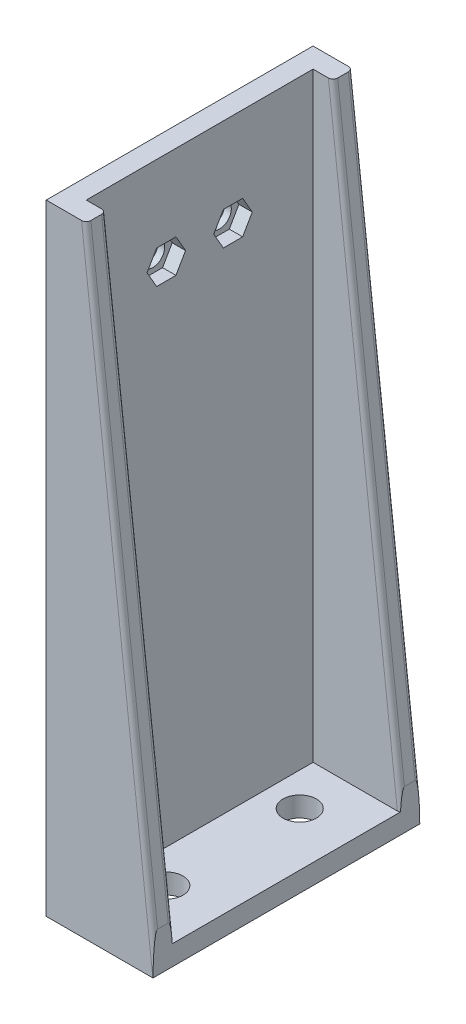
SolidWorks part; units mm, degrees
ref_plane "Front Plane" through (0, 0, 0) normal (0, 0, 1) x (1, 0, 0)
ref_plane "Top Plane" through (0, 0, 0) normal (0, 1, 0) x (1, 0, 0)
ref_plane "Right Plane" through (0, 0, 0) normal (1, 0, 0) x (0, 0, -1)
sketch "Sketch1" plane through (0, 0, 0) normal (0, 1, 0) x (1, 0, 0)
  line L0 (0, 30) -> (0, 10) construction
  line L1 (-8, 0) -> (8, 0)
  line L2 (-8, 0) -> (-8, 40)
  line L3 (-8, 40) -> (8, 40)
  line L4 (8, 0) -> (8, 40)
  line L5 (-3.25, 40) -> (3.25, 40)
  line L9 (-3.25, 0) -> (3.25, 0)
  circle A1 centre (0, 30) radius 2.5
  circle A2 centre (0, 10) radius 2.5
  point P4 (0, 0)
  point P23 (0, 20)
  point P24 (8, 20)
  dimension "D3" = 5
  dimension "D1" = 16
  dimension "D2" = 40
  dimension "D6" = 20
extrude "Boss-Extrude1" add sketch "Sketch1" along normal blind 3
sketch "Sketch2" plane through (0, 3, 0) normal (0, 1, 0) x (1, 0, 0)
  line L0 (-8, 40) -> (8, 40) construction
  line L1 (-8, 0) -> (-5, 0)
  line L2 (-8, 0) -> (-8, 40)
  line L3 (-8, 40) -> (-5, 40)
  line L4 (-5, 0) -> (-5, 40)
  line L5 (8, 0) -> (8, 40) construction
  line L6 (-8, 0) -> (8, 0)
  line L7 (-8, 0) -> (-8, 3)
  line L8 (-8, 3) -> (8, 3)
  line L9 (8, 0) -> (8, 3)
  line L11 (-8, 40) -> (8, 40)
  line L12 (-8, 40) -> (-8, 37)
  line L13 (-8, 37) -> (8, 37)
  line L14 (8, 40) -> (8, 37)
  line M6 (8, 40) -> (-8, 40)
  line M7 (-8, 40) -> (-8, 0)
  line M8 (-8, 0) -> (8, 0)
  line M9 (8, 0) -> (8, 40)
  dimension "D2" = 3
extrude "Boss-Extrude3" add sketch "Sketch2" along normal blind 93 from surface at -3 contours L4 L13 M9 M6 | L13 L4 M7 M6 | L13 L2 L8 L4 | L8 L2 L4 M8 | L8 L4 M8 M9 starting at face at (0, 0, -7.5)
sketch "Sketch3" plane through (0, 0, -40) normal (0, 0, -1) x (-1, 0, 0)
  line L0 (2, 93) -> (-8, 6)
  line L1 (-8, 93) -> (8, 93) construction
  line L2 (-8, 93) -> (-8, 0) construction
  line M8 (8, 93) -> (-8, 93)
  line M9 (-8, 93) -> (-8, 0)
  dimension "D1" = 3
  dimension "D2" = 3
extrude "Cut-Extrude1" cut sketch "Sketch3" against normal through all and the other way through all contours L0 M8 M9
sketch "Sketch4" plane through (-8, 0, 0) normal (-1, 0, 0) x (0, 0, 1)
  line L0 (-15, 79) -> (-25, 79) construction
  line L2 (-13.5566, 76.5) -> (-12.1132, 79)
  line L3 (-12.1132, 79) -> (-13.5566, 81.5)
  line L4 (-13.5566, 81.5) -> (-16.4434, 81.5)
  line L5 (-16.4434, 81.5) -> (-17.8868, 79)
  line L6 (-17.8868, 79) -> (-16.4434, 76.5)
  line L7 (-16.4434, 76.5) -> (-13.5566, 76.5)
  line L8 (-23.5566, 76.5) -> (-22.1132, 79)
  line L9 (-22.1132, 79) -> (-23.5566, 81.5)
  line L10 (-23.5566, 81.5) -> (-26.4434, 81.5)
  line L11 (-26.4434, 81.5) -> (-27.8868, 79)
  line L12 (-27.8868, 79) -> (-26.4434, 76.5)
  line L13 (-26.4434, 76.5) -> (-23.5566, 76.5)
  line L14 (-3, 93) -> (-37, 93) construction
  circle A0 centre (-15, 79) radius 1.75
  circle A1 centre (-25, 79) radius 1.75
  circle A2 centre (-15, 79) radius 2.5 construction
  circle A3 centre (-25, 79) radius 2.5 construction
  point P4 (-20, 93)
  point P19 (-20, 79)
  dimension "D4" = 3.5
  dimension "D1" = 5
  dimension "D2" = 14
  dimension "D3" = 10
extrude "Cut-Extrude2" cut sketch "Sketch4" against normal through all from offset 1 contours A1 | A0 offset against normal yes
extrude "Cut-Extrude3" cut sketch "Sketch4" against normal through all contours A1 | A0
fillet "Fillet1" radius 0.7 4 edges at (3, 49.5, -37) (3, 49.5, 0) (3, 49.5, -3)
